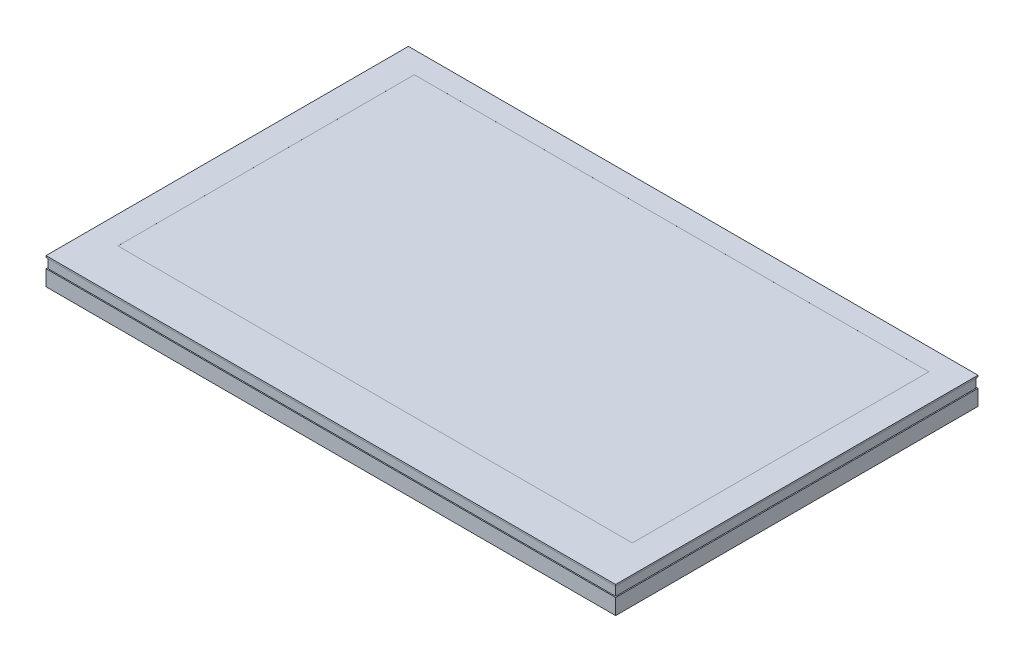
SolidWorks part; units mm, degrees
ref_plane "Front Plane" through (0, 0, 0) normal (0, 0, 1) x (1, 0, 0)
ref_plane "Top Plane" through (0, 0, 0) normal (0, 1, 0) x (1, 0, 0)
ref_plane "Right Plane" through (0, 0, 0) normal (1, 0, 0) x (0, 0, -1)
ref_axis "X Axis" through (-109.587, 0, 0) along (1, 0, 0)
ref_axis "Y Axis" through (0, 0, -140.1599) along (0, 0, 1)
ref_axis "Z Axis" through (0, 50.6832, 0) along (0, -1, 0)
sketch "Sketch1" plane through (0, 0, 0) normal (0, 1, 0) x (1, 0, 0)
  line L1 (-52.71, -33.535) -> (52.71, -33.535)
  line L2 (-52.71, -33.535) -> (-52.71, 33.535)
  line L3 (-52.71, 33.535) -> (52.71, 33.535)
  line L4 (52.71, -33.535) -> (52.71, 33.535)
  line L5 (-52.71, -33.535) -> (52.71, 33.535) construction
  line L6 (-52.71, 33.535) -> (52.71, -33.535) construction
  point P0 (0, 0)
  dimension "D1" = 105.42
  dimension "D2" = 67.07
extrude "Boss-Extrude1" add sketch "Sketch1" along normal blind 2.9
sketch "Sketch2" plane through (0, 2.9, 0) normal (0, 1, 0) x (1, 0, 0)
  line L0 (52.71, -33.535) -> (52.71, 33.535) construction
  line L1 (-52.71, -33.535) -> (52.71, -33.535) construction
  line L2 (-52.71, -33.535) -> (-52.71, 33.535) construction
  line L3 (-52.71, 33.535) -> (52.71, 33.535) construction
  line L4 (52.71, -33.535) -> (52.71, 33.535) construction
  line L5 (-52.51, 33.335) -> (52.51, 33.335)
  line L6 (52.51, -33.335) -> (52.51, 33.335)
  line L7 (52.71, 33.535) -> (-52.71, 33.535) construction
  line L8 (-52.51, -33.335) -> (52.51, -33.335)
  line L9 (-52.51, -33.335) -> (-52.51, 33.335)
  point P0 (0, 0)
  point P10 (-24.5, 33.5)
  point P11 (-52.71, 33.535)
  point P13 (52.71, -33.535)
  dimension "D1" = 0.2
extrude "Boss-Extrude2" add sketch "Sketch2" along normal blind 1.8 separate body
sketch "Sketch3" plane through (0, 4.7, 0) normal (0, 1, 0) x (1, 0, 0)
  line L1 (-52.71, -33.535) -> (52.71, -33.535)
  line L2 (-52.71, -33.535) -> (-52.71, 33.535)
  line L3 (-52.71, 33.535) -> (52.71, 33.535)
  line L4 (52.71, -33.535) -> (52.71, 33.535)
  line L5 (-52.71, -33.535) -> (52.71, 33.535) construction
  line L6 (-52.71, 33.535) -> (52.71, -33.535) construction
  point P0 (0, 0)
extrude "Boss-Extrude3" add sketch "Sketch3" along normal blind 0.3
sketch "Sketch4" plane through (0, 5, 0) normal (0, 1, 0) x (1, 0, 0)
  line L0 (-52.71, 33.535) -> (-52.71, -33.535)
  line L1 (-52.71, -33.535) -> (52.71, -33.535)
  line L2 (52.71, -33.535) -> (52.71, 33.535)
  line L3 (52.71, 33.535) -> (-52.71, 33.535)
  line L4 (-47.61, 29.535) -> (-47.61, -25.335)
  line L5 (-47.61, -25.335) -> (47.61, -25.335)
  line L6 (47.61, -25.335) -> (47.61, 29.535)
  line L7 (47.61, 29.535) -> (-47.61, 29.535)
  dimension "D1" = 5.1
  dimension "D2" = 5.1
  dimension "D3" = 4
  dimension "D4" = 8.2
extrude "Boss-Extrude4" add sketch "Sketch4" along normal blind 0.001
